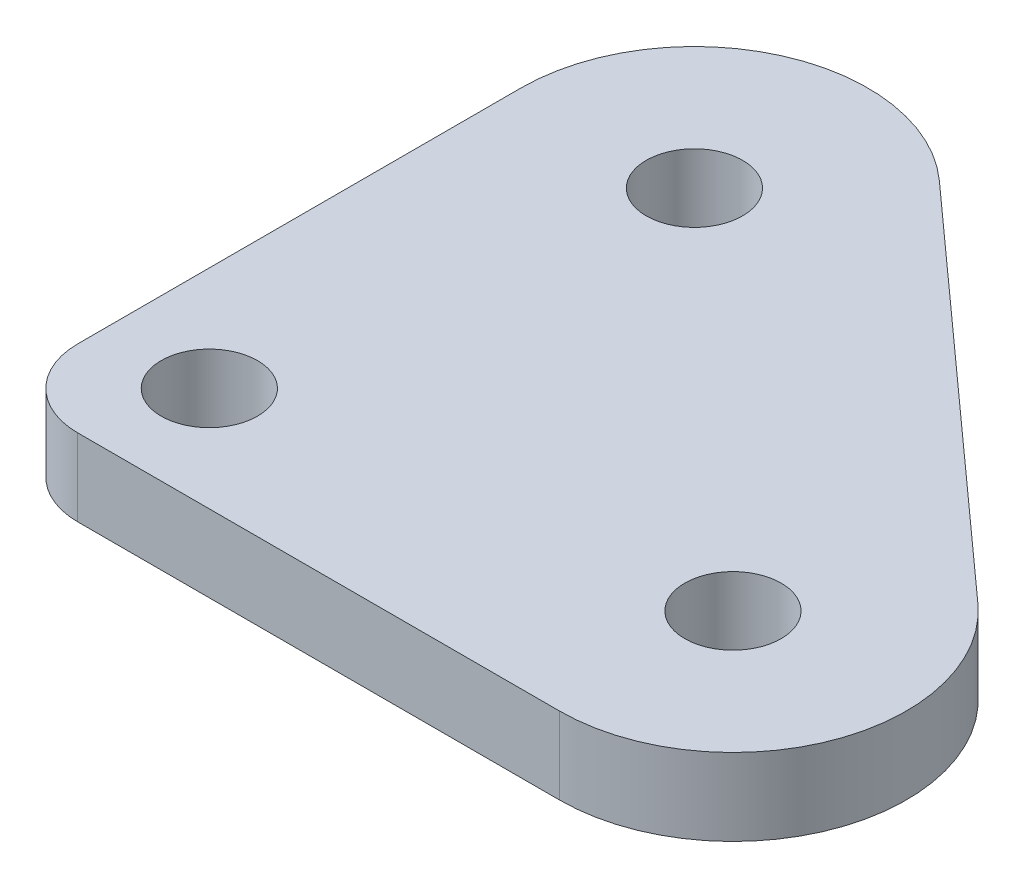
SolidWorks part; units mm, degrees
ref_plane "Front Plane" through (0, 0, 0) normal (0, 0, 1) x (1, 0, 0)
ref_plane "Top Plane" through (0, 0, 0) normal (0, 1, 0) x (1, 0, 0)
ref_plane "Right Plane" through (0, 0, 0) normal (1, 0, 0) x (0, 0, -1)
sketch "Sketch1" plane through (0, 0, 0) normal (0, 1, 0) x (1, 0, 0)
  line L0 (0, 0) -> (20, 0)
  line L1 (20, 0) -> (20, 18)
  line L2 (0, 0) -> (0, 18)
  line L3 (20, -9) -> (-9, -9)
  line L4 (-9, -9) -> (-9, 18)
  line L5 (6.0207, 24.6896) -> (26.0207, 6.6896)
  circle A0 centre (0, 18) radius 9
  circle A1 centre (20, 0) radius 9
  circle A2 centre (0, 18) radius 2.5
  circle A3 centre (20, 0) radius 2.5
  dimension "D4" = 18
  dimension "D5" = 18
  dimension "D6" = 5
  dimension "D7" = 5
  dimension "D1" = 20
  dimension "D2" = 18
  dimension "D3" = 18
extrude "Boss-Extrude1" add sketch "Sketch1" along normal blind 4 contours A1 L0 L2 A0 L4 L3 | A1 L1 L5 A0 L2 L0 | A1 L5 L1 | A2 A0 | A3 L0 A1 L1 | A3 L1 A1 L0 region at (9.3325, 0, -8.9277) region at (-0.27, 0, 1.27) region at (15.9496, 0, -4.0504) region at (14.25, 0, 0.2546) region at (-6.184, 0, -11.816) region at (21.5909, 0, -9.7233)
fillet "Fillet1" radius 4 1 edges at (-9, 2, 9)
sketch "Sketch2" plane through (0, 0, 0) normal (0, -1, 0) x (1, 0, 0)
  line L2 (-3.5858, 9) -> (-3.5858, 3.5858)
  line L3 (20, 9) -> (-5, 9) construction
  line L4 (-3.5858, 3.5858) -> (-9, 3.5858)
  line L5 (-9, 5) -> (-9, -18) construction
  circle A0 centre (-3.5858, 3.5858) radius 2.5
  arc A1 (-5, 9) -> (-9, 5) centre (-5, 5) ccw construction
  dimension "D1" = 5
  dimension "D2" = 2
extrude "Cut-Extrude1" cut sketch "Sketch2" against normal blind 4 contours L4 A0 L2 | L2 A0 L4 region at (-3.2321, 0, 3.2321) region at (-4.6468, 0, 4.6468)
sketch "Sketch3" plane through (0, 4, 0) normal (0, 1, 0) x (1, 0, 0)
  line L0 (-3.5858, -3.5858) -> (20, 0)
  line L1 (20, 0) -> (-3.5858, 0)
  line L2 (-3.5858, 0) -> (-3.5858, -3.5858)
  line L3 (20, 0) -> (0, 18)
  line L4 (0, 18) -> (0, 0)
  line L5 (0, 0) -> (20, 0)
